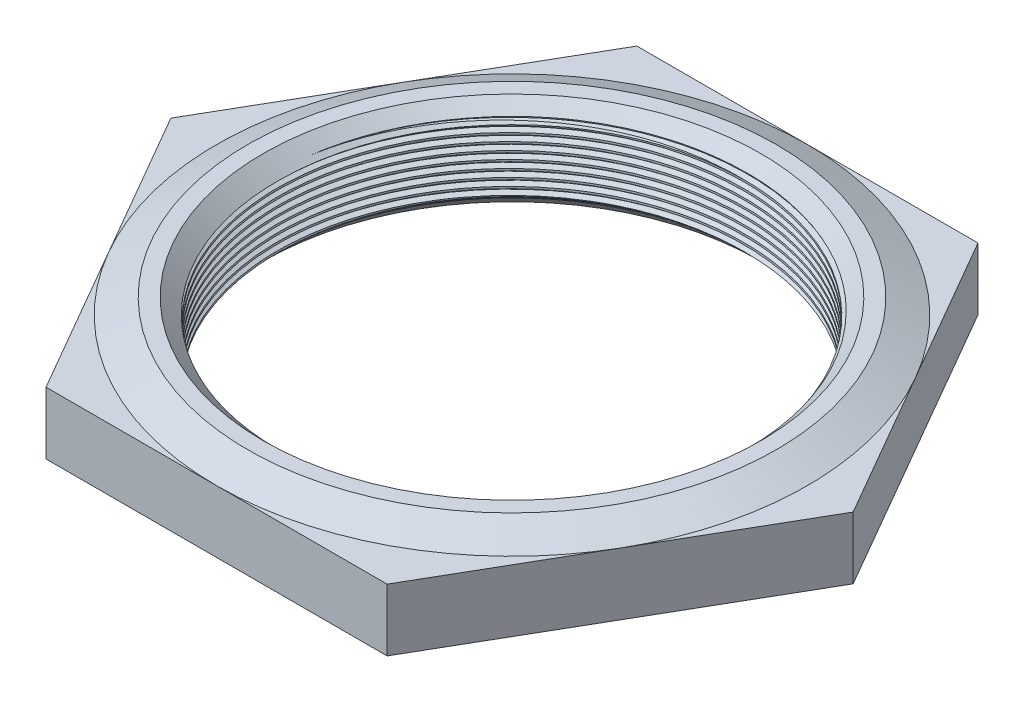
SolidWorks part; units mm, degrees
material "Д16Т ГОСТ 4784-97"
ref_plane "Front Plane" through (0, 0, 0) normal (0, 0, 1) x (1, 0, 0)
ref_plane "Top Plane" through (0, 0, 0) normal (0, 1, 0) x (1, 0, 0)
ref_plane "Right Plane" through (0, 0, 0) normal (1, 0, 0) x (0, 0, -1)
sketch "Sketch1" plane through (0, 0, 0) normal (0, 1, 0) x (1, 0, 0)
  line L1 (5.4848, -9.5) -> (10.9697, 0)
  line L2 (10.9697, 0) -> (5.4848, 9.5)
  line L3 (5.4848, 9.5) -> (-5.4848, 9.5)
  line L4 (-5.4848, 9.5) -> (-10.9697, 0)
  line L5 (-10.9697, 0) -> (-5.4848, -9.5)
  line L6 (-5.4848, -9.5) -> (5.4848, -9.5)
  circle A0 centre (0, 0) radius 9.5 construction
  circle A1 centre (0, 0) radius 7.5
  dimension "D2" = 15
  dimension "D1" = 19
extrude "Boss-Extrude1" add sketch "Sketch1" along normal mid plane 3
chamfer "Chamfer1" distance 0.5 angle 45 2 edges at (0, -1.5, 7.5) (0, 1.5, 7.5)
thread "Thread1" pitch 0.25 method cut trim with start face yes trim with end face yes profile "Thread Profile1" start angle 0, offset 1, length 4, pitch 0.25, diameter 15
ref_plane "Plane1" through (-7.5, 2, 0) normal (0, 0, 1) x (-1, 0, 0)
sketch "Thread Profile1" plane through (-7.5, 2, 0) normal (0, 0, 1) x (-1, 0, 0)
  line L0 (0, 0) -> (0, 0.25) construction
  line L1 (0, 0) -> (0.1353, 0.0781)
  line L2 (0.1353, 0.0781) -> (0.1353, 0.1094)
  line L3 (0.1353, 0.1094) -> (0, 0.1875)
  line L4 (0.1353, 0.0937) -> (0, 0.0937) construction
  line L11 (0, 0) -> (0, 0.1875)
  point P2 (0, 0)
  dimension "Pitch" = 0.25
  dimension "Profile_Angle" = 60
  dimension "Profile_Land" = 0.0312
  dimension "Profile_Height" = 0.1353
sketch "Sketch4" plane through (0, 0, 0) normal (1, 0, 0) x (0, 0, -1)
  line L0 (-9.5, 1) -> (-8.5, 1.5)
  line L1 (-11.5, 1) -> (-11.5, 3.5)
  line L2 (-9.5, 1.5) -> (0, 1.5) construction
  line L3 (-8.5, 1.5) -> (-9.5, 1.5) construction
  line L4 (-9.5, 1.5) -> (-9.5, 1) construction
  line L5 (0.8698, 0) -> (-0.5984, 0) construction
  line L6 (0, -0.5121) -> (0, 2.5118) construction
  line L7 (0, 1.5) -> (0, -1.5) construction
  line L11 (-9.5, 1.5) -> (-9.5, -1.5) construction
  line L12 (-11.5, 3.5) -> (-8.5, 3.5)
  line L13 (-8.5, 3.5) -> (-8.5, 1.5)
  line L14 (-11.5, 1) -> (-9.5, 1)
  line L15 (-9.5, -1.5) -> (-9.5, -1) construction
  line L16 (-8.5, -1.5) -> (-9.5, -1.5) construction
  line L17 (-11.5, -1) -> (-9.5, -1)
  line L18 (-8.5, -3.5) -> (-8.5, -1.5)
  line L19 (-11.5, -3.5) -> (-8.5, -3.5)
  line L20 (-11.5, -1) -> (-11.5, -3.5)
  line L21 (-9.5, -1) -> (-8.5, -1.5)
  dimension "D1" = 2
  dimension "D2" = 2
  dimension "D3" = 8.5
  dimension "D4" = 1
revolve "Cut-Revolve2" cut sketch "Sketch4" angle 360 about L6
